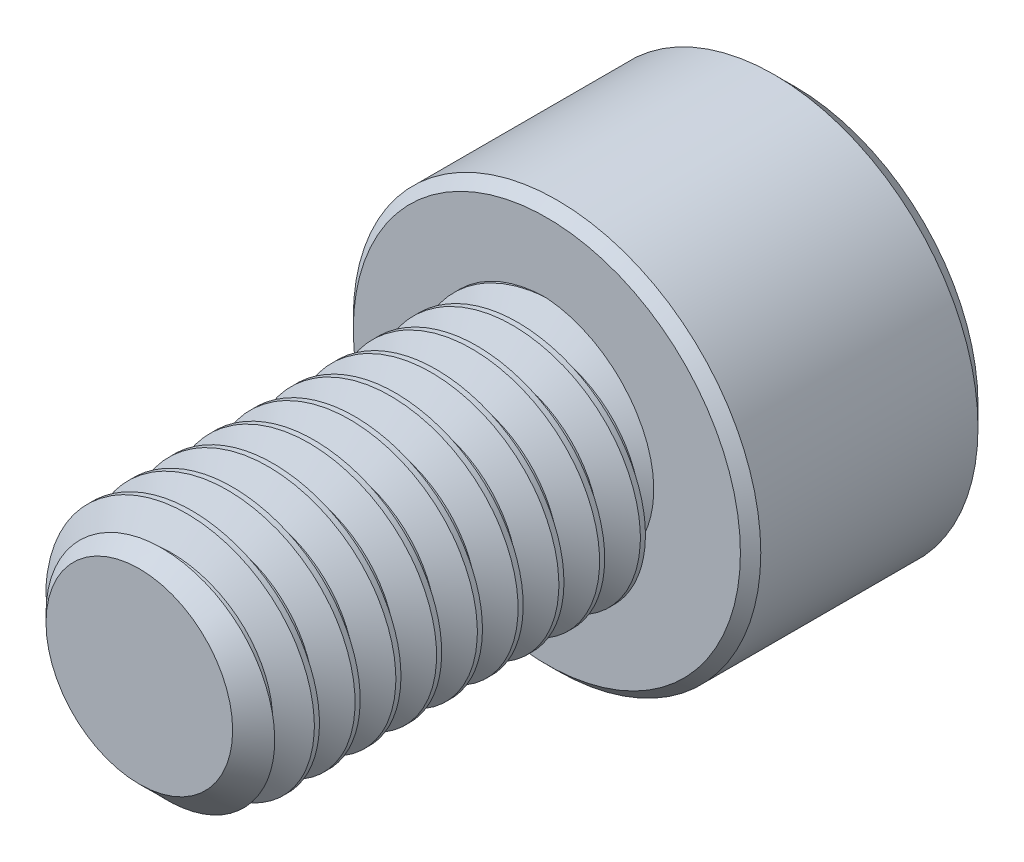
SolidWorks part; units mm, degrees
ref_plane "Front Plane" through (0, 0, 0) normal (0, 0, 1) x (1, 0, 0)
ref_plane "Top Plane" through (0, 0, 0) normal (0, 1, 0) x (1, 0, 0)
ref_plane "Right Plane" through (0, 0, 0) normal (1, 0, 0) x (0, 0, -1)
sketch "Sketch0" plane through (0, 0, 0) normal (1, 0, 0) x (0, 0, -1)
  line L0 (0, 0) -> (7.9375, 0) construction
  point P2 (12.7635, 0)
  point P4 (0, 0)
  dimension "D1" = 7.9375
  dimension "D2" = 4.826
  dimension "Min Thread" = 0
sketch "Sketch1" plane through (0, 0, 0) normal (0, 0, 1) x (1, 0, 0)
  circle A0 centre (0, 0) radius 2.413
  dimension "OD" = 4.826
extrude "Extrude1" add sketch "Sketch1" against normal blind 7.9375
sketch "Sketch2" plane through (0, 0, 0) normal (0, 0, 1) x (1, 0, 0)
  circle A0 centre (0, 0) radius 2.413 construction
  circle A1 centre (0, 0) radius 2.413
curve "Helix/Spiral1" pitch 0.7937 height 8.7312 turns 11 parameters "pitch"=0.7937
chamfer "Chamfer3" distance 0.5953 angle 45 1 edges at (2.413, 0, 0)
sketch "Sketch3" plane through (0, 0, 0) normal (1, 0, 0) x (0, 0, -1)
  line L0 (-0.6945, 2.413) -> (-0.3969, 1.8974)
  line L1 (-0.3969, 1.8974) -> (-0.2977, 1.8974)
  line L2 (-0.2977, 1.8974) -> (0, 2.413)
  line L3 (-0.6945, 2.413) -> (0, 2.413)
  line L4 (-0.3473, 2.413) -> (-0.3473, 1.8974) construction
  line L5 (-0.5457, 2.1552) -> (-0.1488, 2.1552) construction
  line L6 (0, 2.413) -> (0, -2.413) construction
  dimension "D1" = 0.0992
  dimension "D2" = 0.3969
  dimension "D3" = 60
sweep "Cut-Sweep1" cut profiles "Sketch3" path "Helix/Spiral1"
sketch "Sketch5" plane through (0, 0, 0) normal (1, 0, 0) x (0, 0, -1)
  line L0 (7.9375, -1.9083) -> (7.9375, 1.7217) construction
  line L1 (7.9375, 2.413) -> (0, 2.413)
  line L2 (7.9375, 2.413) -> (7.9375, 0)
  line L3 (7.9375, 0) -> (-0.8783, 0)
  line L4 (0, 0) -> (7.9375, 0) construction
  line L5 (0, 2.413) -> (-0.8783, 0)
  line L6 (0, 0) -> (10.4775, 0) construction
  dimension "D1" = 70
  dimension "D3" = 2.54
revolve "partially thread" [suppressed] add sketch "Sketch5" angle 360 about L6
sketch "Sketch6" plane through (0, 0, -7.9375) normal (0, 0, -1) x (-1, 0, 0)
  circle A0 centre (0, 0) radius 3.9688
  dimension "head dia" = 7.9375
extrude "Extrude2" add sketch "Sketch6" along normal blind 4.826
sketch "Sketch7" plane through (0, 0, -12.7635) normal (0, 0, -1) x (-1, 0, 0)
  line L1 (0, 2.2914) -> (-1.9844, 1.1457)
  line L2 (-1.9844, 1.1457) -> (-1.9844, -1.1457)
  line L3 (-1.9844, -1.1457) -> (0, -2.2914)
  line L4 (0, -2.2914) -> (1.9844, -1.1457)
  line L5 (1.9844, -1.1457) -> (1.9844, 1.1457)
  line L6 (1.9844, 1.1457) -> (0, 2.2914)
  circle A0 centre (0, 0) radius 1.9844 construction
  dimension "hex dia" = 3.9688
extrude "Cut-Extrude1" cut sketch "Sketch7" against normal blind 2.9766
sketch "Sketch8" plane through (0, 0, -12.7635) normal (0, 0, -1) x (-1, 0, 0)
  circle A0 centre (0, 0) radius 2.2914
extrude "Cut-Extrude2" cut sketch "Sketch8" against normal through all draft 45
chamfer "Chamfer1" distance 0.3969 angle 45 1 edges at (-3.9688, 0, -12.7635)
chamfer "Chamfer2" distance 0.1984 angle 45 1 edges at (-3.9688, 0, -7.9375)
sketch "Sketch9" plane through (0, 0, 0) normal (1, 0, 0) x (0, 0, -1)
  line L0 (0, 2.413) -> (0, -2.413) construction
  line L1 (1.9844, 2.413) -> (1.9844, -2.413) construction
  line L2 (12.7635, 3.9688) -> (12.7635, -3.9688) construction
  line L3 (7.9375, 3.9688) -> (7.9375, -3.9688) construction
  line L4 (7.9375, 3.7703) -> (7.9375, -3.7703) construction
  line L5 (12.7635, -3.5719) -> (12.7635, 3.5719) construction
  line L6 (7.9375, -3.9688) -> (7.9375, 3.9688) construction
  line L7 (0, 1.8177) -> (0, -1.8177) construction
  line L8 (-0.6945, 2.413) -> (0, 2.413) construction
  line L9 (1.9844, 0) -> (0, 0) construction
  dimension "D1" = 1.9844
equation "\"D3@Helix/Spiral1\" = \"screw length@Extrude1\"+\"pitch@Helix/Spiral1\""
equation "\"D1@Sketch3\" = \"pitch@Helix/Spiral1\"*.125"
equation "\"D2@Sketch3\" = \"pitch@Helix/Spiral1\"*.5"
equation "\"D1@Cut-Extrude1\" = \"hex dia@Sketch7\"*.75"
equation "\"D1@Chamfer1\" = \"head dia@Sketch6\"*.05"
equation "\"D1@Sketch9\" = \"pitch@Helix/Spiral1\"*2.50"
equation "\"D1@Chamfer2\" = \"D1@Chamfer1\"/2"
equation "\"D1@Chamfer3\" = \"pitch@Helix/Spiral1\"*.750"
equation "\"D1@Sketch0\" = \"screw length@Extrude1\""
equation "\"D2@Sketch0\" = \"head depth@Extrude2\""
